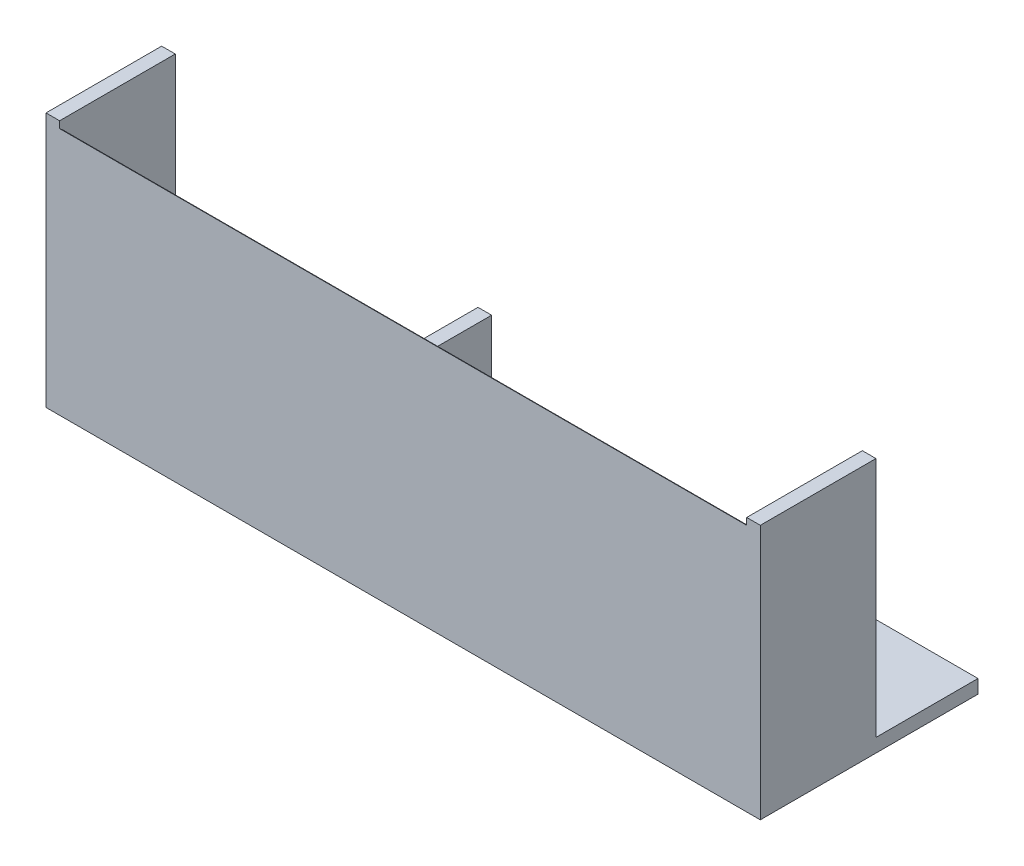
SolidWorks part; units mm, degrees
ref_plane "Front Plane" through (0, 0, 0) normal (0, 0, 1) x (1, 0, 0)
ref_plane "Top Plane" through (0, 0, 0) normal (0, 1, 0) x (1, 0, 0)
ref_plane "Right Plane" through (0, 0, 0) normal (1, 0, 0) x (0, 0, -1)
sketch "Sketch1" plane through (0, 0, 0) normal (0, 0, 1) x (1, 0, 0)
  line L1 (-114.9658, 119.4349) -> (95.0342, 119.4349)
  line L2 (-114.9658, 119.4349) -> (-114.9658, 44.4349)
  line L3 (-114.9658, 44.4349) -> (95.0342, 44.4349)
  line L4 (95.0342, 119.4349) -> (95.0342, 44.4349)
  line L5 (-114.9658, 119.4349) -> (95.0342, 44.4349) construction
  line L6 (-114.9658, 44.4349) -> (95.0342, 119.4349) construction
  point P0 (-9.9658, 81.9349)
  dimension "D1" = 75
  dimension "D2" = 210
extrude "Boss-Extrude1" add sketch "Sketch1" along normal blind 4
sketch "Sketch2" plane through (0, 0, 0) normal (0, 0, 1) x (1, 0, 0)
  line L0 (95.0342, 44.4349) -> (95.0342, 119.4349) construction
  line L1 (-114.9658, 44.4349) -> (95.0342, 44.4349)
  line L2 (-114.9658, 44.4349) -> (-114.9658, 48.4349)
  line L3 (-114.9658, 48.4349) -> (95.0342, 48.4349)
  line L4 (95.0342, 44.4349) -> (95.0342, 48.4349)
  dimension "D1" = 4
extrude "Boss-Extrude2" add sketch "Sketch2" against normal blind 60
sketch "Sketch3" plane through (0, 0, 0) normal (0, 0, 1) x (1, 0, 0)
  line L0 (-9.9658, 9.1029) -> (-9.9658, 130.6974) construction
  line L1 (95.0342, 48.4349) -> (95.0342, 119.4349) construction
  line L2 (95.0342, 48.4349) -> (-114.9658, 48.4349) construction
  line L3 (-114.9658, 119.4349) -> (-110.9658, 119.4349)
  line L4 (-114.9658, 119.4349) -> (-114.9658, 48.4349)
  line L5 (-114.9658, 48.4349) -> (-110.9658, 48.4349)
  line L6 (-110.9658, 119.4349) -> (-110.9658, 48.4349)
  line L8 (95.0342, 119.4349) -> (91.0342, 119.4349)
  line L9 (95.0342, 119.4349) -> (95.0342, 48.4349)
  line L10 (95.0342, 48.4349) -> (91.0342, 48.4349)
  line L11 (91.0342, 119.4349) -> (91.0342, 48.4349)
  dimension "D1" = 4
  dimension "105" = 105
extrude "Boss-Extrude3" add sketch "Sketch3" against normal blind 30
fillet "Fillet1" radius 10 1 edges at (-9.9658, 119.4349, 0)
sketch "Sketch5" plane through (0, 0, 0) normal (0, 0, -1) x (-1, 0, 0)
  line L0 (9.9658, 57.2144) -> (9.9658, 123.7789) construction
  line L1 (-95.0342, 48.4349) -> (-95.0342, 119.4349) construction
  line L2 (-91.0342, 48.4349) -> (110.9658, 48.4349) construction
  line L3 (11.9658, 48.4349) -> (7.9658, 48.4349)
  line L4 (11.9658, 48.4349) -> (11.9658, 109.4349)
  line L5 (11.9658, 109.4349) -> (7.9658, 109.4349)
  line L6 (7.9658, 48.4349) -> (7.9658, 109.4349)
  line L7 (110.9658, 109.4349) -> (-91.0342, 109.4349) construction
  dimension "D1" = 105
  dimension "D2" = 4
  dimension "D3" = 2
extrude "Boss-Extrude4" add sketch "Sketch5" along normal blind 20
